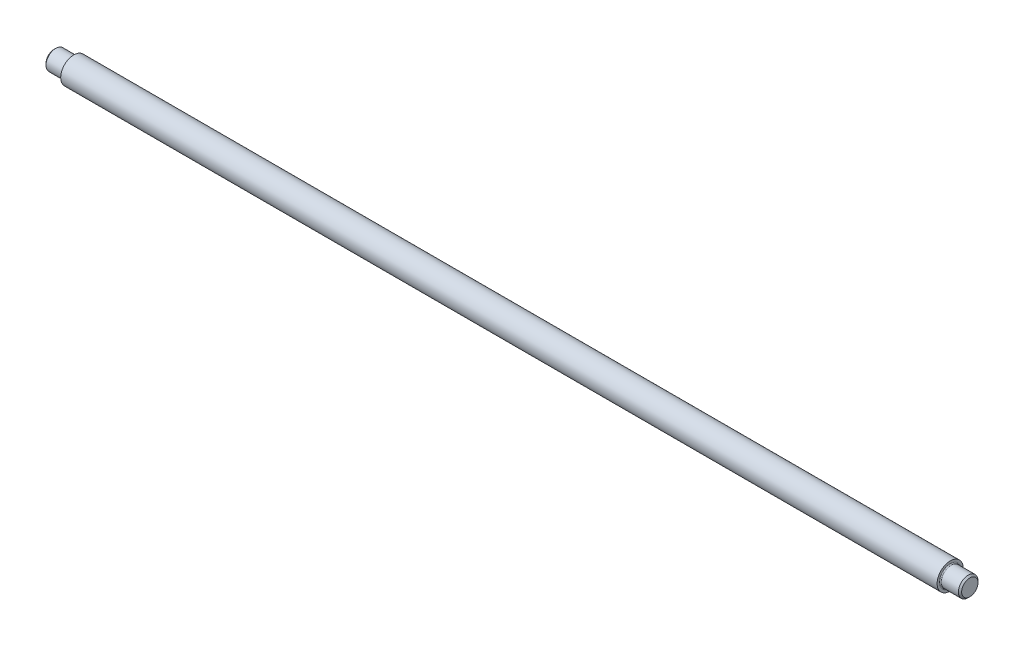
SolidWorks part; units mm, degrees
ref_plane "Front Plane" through (0, 0, 0) normal (0, 0, 1) x (1, 0, 0)
ref_plane "Top Plane" through (0, 0, 0) normal (0, 1, 0) x (1, 0, 0)
ref_plane "Right Plane" through (0, 0, 0) normal (1, 0, 0) x (0, 0, -1)
sketch "Sketch1" plane through (0, 0, 0) normal (0, 0, 1) x (1, 0, 0)
  line L0 (0, 2.5) -> (0, 0)
  line L1 (0, 0) -> (280, 0)
  line L2 (280, 0) -> (280, 2.5)
  line L3 (280, 2.5) -> (279.5, 3)
  line L4 (279.5, 3) -> (274.3, 3)
  line L5 (274, 3.3) -> (274, 4)
  line L6 (274, 4) -> (6, 4)
  line L7 (6, 4) -> (6, 3.3)
  line L8 (5.7, 3) -> (0.5, 3)
  line L9 (0.5, 3) -> (0, 2.5)
  line L10 (0, 0) -> (280, 0) construction
  arc A0 (274.3, 3) -> (274, 3.3) centre (274.3, 3.3) cw
  arc A1 (6, 3.3) -> (5.7, 3) centre (5.7, 3.3) cw
revolve "Revolve1" add sketch "Sketch1" angle 360 about L10 reverse direction yes
